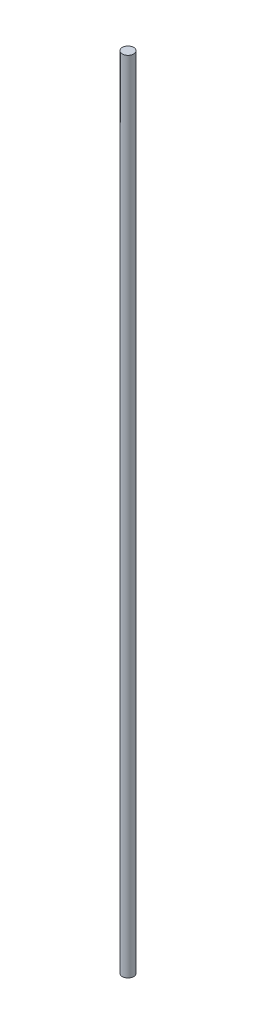
SolidWorks part; units mm, degrees
material "AISI 1020"
ref_plane "Front Plane" through (0, 0, 0) normal (0, 0, 1) x (1, 0, 0)
ref_plane "Top Plane" through (0, 0, 0) normal (0, 1, 0) x (1, 0, 0)
ref_plane "Right Plane" through (0, 0, 0) normal (1, 0, 0) x (0, 0, -1)
sketch "Sketch1" plane through (0, 0, 0) normal (0, 1, 0) x (1, 0, 0)
  circle A0 centre (0, 0) radius 2.5
  dimension "D1" = 5
extrude "Boss-Extrude1" add sketch "Sketch1" along normal blind 175 and the other way blind 175
cosmetic thread "Cosmetic Thread1" parameters "D2"=4
